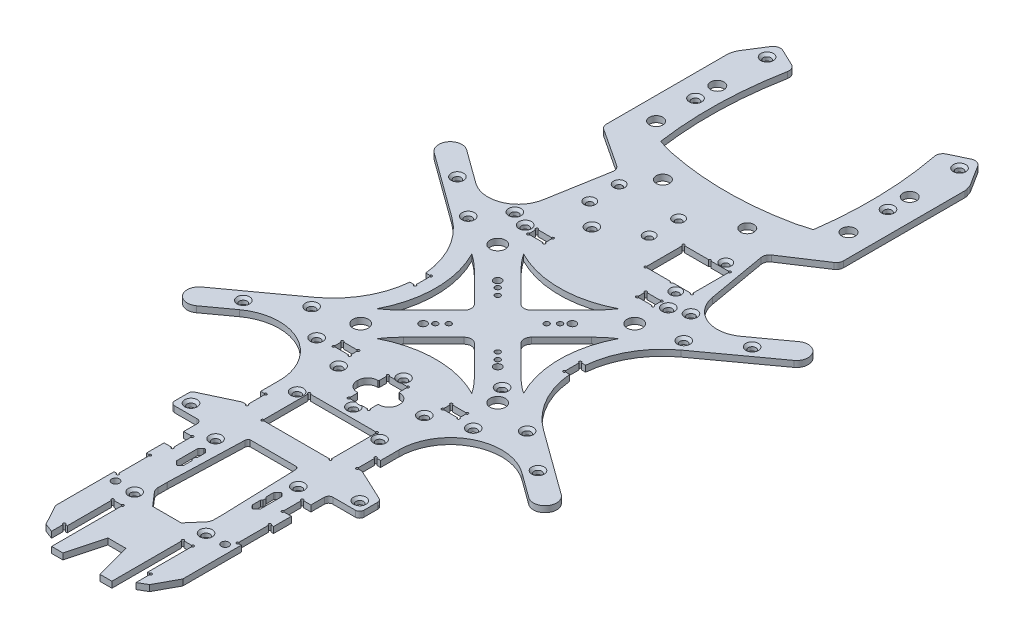
SolidWorks part; units mm, degrees
material "PPS"
ref_plane "前视基准面" through (0, 0, 0) normal (0, 0, 1) x (1, 0, 0)
ref_plane "上视基准面" through (0, 0, 0) normal (0, 1, 0) x (1, 0, 0)
ref_plane "右视基准面" through (0, 0, 0) normal (1, 0, 0) x (0, 0, -1)
sketch "草图1" plane through (0, 0, 0) normal (0, 1, 0) x (1, 0, 0)
  line L0 (-126.4995, 0) -> (116.8967, 0) construction
  line L1 (121.619, 121.619) -> (-121.619, -121.619) construction
  line L2 (0, 104.5414) -> (0, -99.6328) construction
  line L3 (-108.3893, 108.3893) -> (124.9236, -124.9236) construction
  line L4 (0, 0) -> (86.3378, -62.728) construction
  line L5 (21.4, 65.75) -> (28.6, 65.75)
  line L6 (20.9, 50.75) -> (20.9, 65.25)
  line L19 (21.4, 50.25) -> (28.6, 50.25)
  line L20 (30.0249, 79.2189) -> (48.4165, 91.3178)
  line L21 (0, 82.79) -> (0, 88.225) construction
  line L23 (-25.2781, 96.1111) -> (-31.2329, 97.7907)
  line L25 (24.5, -95.1) -> (26, -95.1) construction
  line L35 (73.5338, -47.5541) -> (46.853, -28.1694)
  line L38 (-14.1474, -105.2622) -> (-15.2326, -104.177)
  line L39 (-48.4165, 91.3178) -> (-48.4165, 143.0516)
  line L40 (-30.0249, 79.2189) -> (-48.4165, 91.3178)
  line L42 (26, -95.1) -> (26, -102.35)
  line L64 (20.9, 58) -> (32.4846, 58) construction
  line L65 (25, 65.75) -> (25, 50.25) construction
  line L66 (29.1, 65.25) -> (29.1, 50.75)
  line L69 (-39.335, 68.135) -> (3.7462, 68.135) construction
  line L72 (26, -102.35) -> (22.5, -102.35)
  line L80 (-15.9397, -104.177) -> (-16.9545, -105.1918)
  line L82 (4.1009, -56.25) -> (4.1009, -53.2975)
  line L83 (-3.6009, -56.75) -> (3.6009, -56.75)
  line L84 (3.6009, -40.75) -> (-3.5991, -40.75)
  line L85 (4.1009, -41.25) -> (4.1009, -44.2025)
  line L86 (-4.1009, -56.25) -> (-4.1009, -53.2961)
  line L87 (-4.1009, -44.2011) -> (-4.1009, -41.2481)
  line L88 (-4.5484, -52.9461) -> (-4.4509, -52.9461)
  line L89 (-8.5484, -48.9461) -> (-8.5484, -48.5511)
  line L90 (8.5484, -48.9475) -> (8.5484, -48.5525)
  line L91 (4.4509, -52.9475) -> (4.5484, -52.9475)
  line L92 (4.5484, -44.5525) -> (4.4509, -44.5525)
  line L93 (-4.5484, -44.5511) -> (-4.4509, -44.5511)
  line L97 (19, -62.5) -> (19, -100.5) construction
  line L98 (19, -100.5) -> (-19, -100.5) construction
  line L99 (-19, -62.5) -> (-19, -100.5) construction
  line L100 (22.5, -102.35) -> (22.5, -110.35)
  line L101 (16.4174, -141.0041) -> (16.4174, -159.5041)
  line L102 (16.4174, -141.0041) -> (12.3174, -141.0041)
  line L103 (12.3174, -141.0041) -> (12.3174, -170.0041)
  line L104 (17.705, -159.5041) -> (16.4174, -159.5041)
  line L105 (17.705, -165.5542) -> (17.705, -159.5041)
  line L106 (-3.8169, -155.5041) -> (-7.6919, -170.0041)
  line L107 (-7.6919, -170.0041) -> (-12.3174, -170.0041)
  line L108 (21.2406, -163.4622) -> (17.705, -165.5542)
  line L109 (-17.705, -164.6632) -> (-17.705, -159.5041)
  line L110 (-17.705, -159.5041) -> (-16.4174, -159.5041)
  line L111 (-12.3174, -141.0041) -> (-12.3174, -170.0041)
  line L112 (-16.4174, -141.0041) -> (-12.3174, -141.0041)
  line L113 (-16.4174, -141.0041) -> (-16.4174, -159.5041)
  line L114 (7.4592, -170.0041) -> (12.3174, -170.0041)
  line L115 (-3.8169, -155.5041) -> (3.6009, -155.5041)
  line L116 (3.6009, -155.5041) -> (7.4592, -170.0041)
  line L117 (-21.3412, -163.277) -> (-17.705, -164.6632)
  line L118 (-11.3955, -123.6362) -> (-10.3849, -92.9161)
  line L119 (-10.5767, -129.7197) -> (-5.85, -135.1929)
  line L120 (-5.85, -135.1929) -> (5.85, -135.1929)
  line L121 (-11.3974, -127.5138) -> (-11.3974, -123.7472)
  line L122 (22.5, -110.35) -> (26, -110.35)
  line L123 (26, -130.7962) -> (26, -154.7028)
  line L124 (26, -154.7028) -> (21.2406, -163.4622)
  line L125 (-26, -154.7028) -> (-21.3412, -163.277)
  line L126 (-26, -130.7962) -> (-26, -154.7028)
  line L127 (26, -110.35) -> (26, -117.6)
  line L128 (26, -117.6) -> (24.5, -117.6)
  line L129 (24.5, -117.6) -> (24.5, -130.7962)
  line L130 (24.5, -130.7962) -> (26, -130.7962)
  line L132 (-24.5, -130.7962) -> (-26, -130.7962)
  line L133 (-24.5, -117.6) -> (-24.5, -130.7962)
  line L134 (-26, -117.6) -> (-24.5, -117.6)
  line L135 (-26, -110.35) -> (-26, -117.6)
  line L136 (-22.5, -110.35) -> (-26, -110.35)
  line L137 (-22.5, -102.35) -> (-22.5, -110.35)
  line L138 (-26, -102.35) -> (-22.5, -102.35)
  line L139 (-26, -95.1) -> (-26, -102.35)
  line L140 (-24.5, -95.1) -> (-26, -95.1) construction
  line L142 (-73.5338, 47.5541) -> (-46.853, 28.1694)
  line L143 (-73.5338, -47.5541) -> (-46.853, -28.1694)
  line L149 (48.4165, 91.3178) -> (48.4165, 143.0516)
  line L150 (0, -114.8485) -> (0, -146.3095) construction
  line L151 (-9.5, -91.6929) -> (9.5, -91.6929)
  line L152 (10.5767, -129.7197) -> (5.85, -135.1929)
  line L153 (11.3974, -127.5138) -> (11.3974, -123.7472)
  line L154 (11.3955, -123.6362) -> (10.3849, -92.9161)
  line L155 (-19, -62.5) -> (19, -62.5) construction
  line L166 (-13.866, -63.21) -> (13.866, -63.21)
  line L171 (-13.866, -63.21) -> (-13.866, -82.21)
  line L174 (-13.866, -82.21) -> (13.866, -82.21)
  line L177 (13.866, -63.21) -> (13.866, -82.21)
  line L180 (73.5338, 47.5541) -> (46.853, 28.1694)
  line L181 (44.0442, 32) -> (60.2246, 43.7557) construction
  line L183 (25.2781, 96.1111) -> (31.2329, 97.7907)
  line L184 (47.6512, 145.4189) -> (48.4165, 143.0516)
  line L188 (-47.6512, 145.4189) -> (-40.8875, 156.1591)
  line L190 (47.6512, 145.4189) -> (40.8875, 156.1591)
  line L192 (31.6811, 151.7709) -> (40.8875, 156.1591)
  line L193 (-40.8875, 156.1591) -> (-31.6811, 151.7709)
  line L194 (-47.6512, 145.4189) -> (-48.4165, 143.0516)
  line L195 (67.9498, 55.2397) -> (54.1532, 45.2159)
  line L196 (30.0249, 79.2189) -> (34.5797, 53.1425)
  line L197 (-30.0249, 79.2189) -> (-34.5797, 53.1425)
  line L198 (-67.9498, 55.2397) -> (-54.1532, 45.2159)
  line L199 (57.77, -47.8437) -> (67.9498, -55.2397)
  line L200 (24.5, -64.7956) -> (24.5, -95.1) construction
  line L201 (-24.5, -64.7956) -> (-24.5, -95.1) construction
  line L202 (-57.77, -47.8437) -> (-67.9498, -55.2397)
  line L203 (26, -95.1) -> (38.6804, -95.1)
  line L204 (38.6804, -95.1) -> (38.6804, -86.6)
  line L205 (38.6804, -86.6) -> (24.5, -79.9478)
  line L207 (-38.6804, -86.6) -> (-24.5, -79.9478)
  line L208 (-38.6804, -95.1) -> (-38.6804, -86.6)
  line L209 (-26, -95.1) -> (-38.6804, -95.1)
  line L210 (-24.5, -64.7956) -> (-24.5, -79.9478) construction
  line L211 (-16.9545, -114.3989) -> (-15.8693, -115.4841)
  line L212 (-15.1622, -115.4841) -> (-14.1474, -114.4693)
  line L213 (-17.1009, -105.5454) -> (-17.1009, -114.0454)
  line L214 (-14.0009, -105.6158) -> (-14.0009, -114.1158) construction
  line L221 (-14.0009, -105.6158) -> (-14.0009, -108.6704)
  line L222 (-14.0009, -108.6704) -> (-14.5009, -109.1704)
  line L223 (-14.5009, -109.1704) -> (-14.5009, -110.4204)
  line L224 (-14.5009, -110.4204) -> (-14.0009, -110.9204)
  line L225 (-14.0009, -110.9204) -> (-14.0009, -114.1158)
  line L226 (-17.1009, -109.7954) -> (-13.2317, -109.7954) construction
  line L227 (14.5009, -110.4204) -> (14.0009, -110.9204)
  line L228 (14.5009, -109.1704) -> (14.5009, -110.4204)
  line L229 (14.0009, -108.6704) -> (14.5009, -109.1704)
  line L230 (14.0009, -105.6158) -> (14.0009, -108.6704)
  line L231 (14.1474, -105.2622) -> (15.2326, -104.177)
  line L232 (15.9397, -104.177) -> (16.9545, -105.1918)
  line L233 (17.1009, -105.5454) -> (17.1009, -114.0454)
  line L234 (16.9545, -114.3989) -> (15.8693, -115.4841)
  line L235 (15.1622, -115.4841) -> (14.1474, -114.4693)
  line L236 (14.0009, -110.9204) -> (14.0009, -114.1158)
  line L237 (-24.5, -72.3717) -> (-22.5, -72.3717)
  line L238 (-22.5, -72.3717) -> (-22.5, -79.9478)
  line L239 (-22.5, -79.9478) -> (-24.5, -79.9478)
  line L240 (-24.5, -64.7956) -> (-24.5, -72.3717)
  line L241 (22.5, -79.9478) -> (24.5, -79.9478)
  line L242 (24.5, -64.7956) -> (24.5, -72.3717)
  line L243 (24.5, -72.3717) -> (22.5, -72.3717)
  line L244 (22.5, -72.3717) -> (22.5, -79.9478)
  circle A0 centre (10, 10) radius 1.075
  circle A1 centre (12.75, 12.75) radius 1.075
  circle A2 centre (15.25, 15.25) radius 1.55
  circle A3 centre (-15.25, 15.25) radius 1.55
  circle A4 centre (-12.75, 12.75) radius 1.075
  circle A5 centre (-10, 10) radius 1.075
  circle A6 centre (-10, -10) radius 1.075
  circle A7 centre (-12.75, -12.75) radius 1.075
  circle A8 centre (-15.25, -15.25) radius 1.55
  circle A9 centre (15.25, -15.25) radius 1.55
  circle A10 centre (12.75, -12.75) radius 1.075
  circle A11 centre (10, -10) radius 1.075
  circle A14 centre (28, -28) radius 3.15
  circle A15 centre (-28, -28) radius 3.15
  circle A16 centre (25, 68.2) radius 1.3
  arc A17 (20.9, 65.25) -> (21.4, 65.75) centre (20.9, 65.75) cw
  arc A18 (20.9, 50.75) -> (21.4, 50.25) centre (20.9, 50.25) ccw
  circle A31 centre (25, 47.8) radius 1.3
  circle A34 centre (17.238, 84.7633) radius 2.75
  circle A35 centre (-17.238, 84.7633) radius 2.75
  circle A36 centre (-39.335, 104.0823) radius 2.75
  circle A37 centre (-39.335, 129.0823) radius 2.75
  circle A38 centre (-28, 28) radius 3.15
  circle A39 centre (28, 28) radius 3.15
  circle A43 centre (44.0442, -32) radius 1.55
  circle A44 centre (60.2246, -43.7557) radius 1.55
  circle A47 centre (-60.2246, -43.7557) radius 1.55
  arc A63 (29.1, 65.25) -> (28.6, 65.75) centre (29.1, 65.75) ccw
  arc A64 (29.1, 50.75) -> (28.6, 50.25) centre (29.1, 50.25) cw
  circle A65 centre (-24.5, 74.15) radius 1.3
  circle A68 centre (-24.5, 62.12) radius 1.3
  circle A71 centre (-44.0442, -32) radius 1.55
  circle A72 centre (60.2246, 43.7557) radius 1.55
  circle A73 centre (44.0442, 32) radius 1.55
  circle A74 centre (-44.0442, 32) radius 1.55
  circle A75 centre (-60.2246, 43.7557) radius 1.55
  arc A77 (67.9498, -55.2397) -> (73.5338, -47.5541) centre (70.7418, -51.3969) ccw
  arc A82 (-14.0009, -105.6158) -> (-14.1474, -105.2622) centre (-14.5009, -105.6158) ccw
  arc A83 (-15.2326, -104.177) -> (-15.9397, -104.177) centre (-15.5861, -104.5306) ccw
  arc A84 (-17.1009, -105.5454) -> (-16.9545, -105.1918) centre (-16.6009, -105.5454) cw
  arc A85 (-4.1009, -56.25) -> (-3.6009, -56.75) centre (-4.1009, -56.75) ccw
  arc A86 (4.1009, -56.25) -> (3.6009, -56.75) centre (4.1009, -56.75) cw
  arc A87 (4.1009, -41.25) -> (3.6009, -40.75) centre (4.1009, -40.75) ccw
  arc A88 (-4.1009, -41.2481) -> (-3.5991, -40.75) centre (-4.0991, -40.7481) cw
  arc A89 (8.5484, -48.5525) -> (4.5484, -44.5525) centre (4.5484, -48.5525) ccw
  arc A90 (-4.5484, -44.5511) -> (-8.5484, -48.5511) centre (-4.5484, -48.5511) ccw
  arc A91 (-4.5484, -52.9461) -> (-8.5484, -48.9461) centre (-4.5484, -48.9461) cw
  arc A92 (8.5484, -48.9475) -> (4.5484, -52.9475) centre (4.5484, -48.9475) cw
  arc A93 (4.1009, -44.2025) -> (4.4509, -44.5525) centre (4.4509, -44.2025) ccw
  arc A94 (4.1009, -53.2975) -> (4.4509, -52.9475) centre (4.4509, -53.2975) cw
  arc A95 (-4.1009, -44.2011) -> (-4.4509, -44.5511) centre (-4.4509, -44.2011) cw
  arc A96 (-4.1009, -53.2961) -> (-4.4509, -52.9461) centre (-4.4509, -53.2961) ccw
  circle A103 centre (-22.3899, -133.8062) radius 1.55
  circle A104 centre (22.3899, -133.8062) radius 1.55
  circle A105 centre (-16.9, -98.4) radius 1.55
  circle A106 centre (16.9, -98.4) radius 1.55
  arc A107 (-9.5, -91.6929) -> (-10.3849, -92.9161) centre (-9.0356, -92.9605) ccw
  arc A108 (-11.3974, -123.7472) -> (-11.3955, -123.6362) centre (-8.0224, -123.7472) cw
  arc A109 (-10.5767, -129.7197) -> (-11.3974, -127.5138) centre (-8.0224, -127.5138) cw
  circle A110 centre (-14.6009, -133.8062) radius 1.55
  circle A111 centre (14.6009, -133.8062) radius 1.55
  arc A112 (10.5767, -129.7197) -> (11.3974, -127.5138) centre (8.0224, -127.5138) ccw
  arc A113 (11.3974, -123.7472) -> (11.3955, -123.6362) centre (8.0224, -123.7472) ccw
  arc A114 (9.5, -91.6929) -> (10.3849, -92.9161) centre (9.0356, -92.9605) cw
  circle A143 centre (-16.866, -65.108) radius 1.55
  circle A144 centre (16.866, -65.108) radius 1.55
  circle A145 centre (0, -38.5) radius 1.55
  circle A146 centre (0, -59) radius 1.55
  arc A147 (67.9498, 55.2397) -> (73.5338, 47.5541) centre (70.7418, 51.3969) cw
  arc A148 (46.853, 28.1694) -> (46.853, -28.1694) centre (67.3193, 0) ccw
  circle A149 centre (44.0442, -32) radius 6 construction
  arc A151 (-67.9498, 55.2397) -> (-73.5338, 47.5541) centre (-70.7418, 51.3969) ccw
  arc A153 (-46.853, 28.1694) -> (-46.853, -28.1694) centre (-67.3193, 0) cw
  arc A154 (-67.9498, -55.2397) -> (-73.5338, -47.5541) centre (-70.7418, -51.3969) cw
  circle A158 centre (39.335, 129.0823) radius 2.75
  circle A159 centre (39.335, 104.0823) radius 2.75
  arc A160 (-25.2781, 96.1111) -> (25.2781, 96.1111) centre (0, 215.2587) ccw
  circle A161 centre (-36, 43) radius 1.55
  circle A164 centre (36, 43) radius 1.55
  circle A165 centre (-32, -42) radius 1.55
  circle A166 centre (32, -42) radius 1.55
  circle A171 centre (-39.335, 149.4323) radius 1.55
  arc A176 (30.0249, 148.5011) -> (31.6811, 151.7709) centre (32.9719, 149.0628) cw
  arc A178 (30.0249, 148.5011) -> (31.2329, 97.7907) centre (-122.0773, 119.5082) cw
  arc A180 (-30.0249, 148.5011) -> (-31.2329, 97.7907) centre (122.0773, 119.5082) ccw
  arc A181 (-31.6811, 151.7709) -> (-30.0249, 148.5011) centre (-32.9719, 149.0628) cw
  arc A182 (54.1532, 45.2159) -> (34.5797, 53.1425) centre (46.8385, 55.2837) cw
  arc A183 (-54.1532, 45.2159) -> (-34.5797, 53.1425) centre (-46.8385, 55.2837) ccw
  circle A185 centre (39.335, 149.4323) radius 1.55
  arc A186 (57.77, -47.8437) -> (24.5, -64.7956) centre (45.4537, -64.7956) ccw
  arc A187 (-57.77, -47.8437) -> (-24.5, -64.7956) centre (-45.4537, -64.7956) cw
  circle A188 centre (34.5, -90.85) radius 1.55
  circle A189 centre (-34.5, -90.85) radius 1.55
  circle A190 centre (39.335, 120.1823) radius 1.55
  circle A191 centre (-39.335, 120.1823) radius 1.55
  arc A192 (-17.1009, -114.0454) -> (-16.9545, -114.3989) centre (-16.6009, -114.0454) ccw
  arc A193 (-15.8693, -115.4841) -> (-15.1622, -115.4841) centre (-15.5157, -115.1306) ccw
  arc A194 (-14.0009, -114.1158) -> (-14.1474, -114.4693) centre (-14.5009, -114.1158) cw
  arc A195 (14.0009, -105.6158) -> (14.1474, -105.2622) centre (14.5009, -105.6158) cw
  arc A196 (15.2326, -104.177) -> (15.9397, -104.177) centre (15.5861, -104.5306) cw
  arc A197 (17.1009, -105.5454) -> (16.9545, -105.1918) centre (16.6009, -105.5454) ccw
  arc A198 (17.1009, -114.0454) -> (16.9545, -114.3989) centre (16.6009, -114.0454) cw
  arc A199 (15.8693, -115.4841) -> (15.1622, -115.4841) centre (15.5157, -115.1306) cw
  arc A200 (14.0009, -114.1158) -> (14.1474, -114.4693) centre (14.5009, -114.1158) ccw
  circle A201 centre (-0.2, 62.12) radius 1.3
  circle A202 centre (-0.2, 74.15) radius 1.3
  point P104 (-32.5, 0)
  point P105 (32.5, 0)
  point P214 (38.6804, -90.85)
  point P354 (0, -135.1929)
  point P361 (7.3036, -118.1341)
  point P364 (0, -91.6929)
  dimension "D2" = 2.15
  dimension "D5" = 3.1
  dimension "D7" = 3.1
  dimension "D8" = 36
  dimension "D10" = 0.5
  dimension "D11" = 3.1
  dimension "D20" = 2.6
  dimension "D22" = 3.1
  dimension "D32" = 7.25
  dimension "D12" = 24.3
  dimension "D15" = 19
  dimension "D13" = 3
  dimension "D9" = 3.1
  dimension "D25" = 4.75
  dimension "D26" = 13
  dimension "D31" = 12
  dimension "D41" = 96.833
  dimension "D49" = 32
  dimension "D54" = 45.35
  dimension "D59" = 8.5
  dimension "D61" = 6.3
  dimension "D70" = 2.6
  dimension "D3" = 10
  dimension "D4" = 2.75
  dimension "D6" = 2.5
  dimension "D14" = 58
  dimension "D16" = 2.608
  dimension "D17" = 15.5
  dimension "D18" = 2.45
  dimension "D19" = 8.2
  dimension "D21" = 12.03
  dimension "D23" = 2.25
  dimension "D24" = 2.25
  dimension "D27" = 20
  dimension "D28" = 25
  dimension "D29" = 25
  dimension "D30" = 32
  dimension "D33" = 1.5
  dimension "D34" = 2.1
  dimension "D35" = 10.5
  dimension "D36" = 14.5
  dimension "D37" = 4
  dimension "D38" = 4.1
  dimension "D39" = 8
  dimension "D40" = 65
  dimension "D42" = 9.5
  dimension "D43" = 43
  dimension "D44" = 43.5
  dimension "D45" = 40.75
  dimension "D46" = 7.2
  dimension "D47" = 16
  dimension "D48" = 62.5
  dimension "D50" = 38
  dimension "D51" = 7.2
  dimension "D52" = 36
  dimension "D53" = 42
  dimension "D55" = 90.85
  dimension "D56" = 5.5
  dimension "D57" = 38
  dimension "D58" = 34.5
  dimension "D60" = 56
  dimension "D62" = 5.85
  dimension "D63" = 29.25
  dimension "D64" = 8.5
  dimension "D65" = 1.25
  dimension "D66" = 0.5
  dimension "D67" = 2
  dimension "D68" = 24.5
  dimension "D69" = 82.21
extrude "凸台-拉伸1" add sketch "草图1" along normal blind 2.5
sketch "草图6" plane through (0, 2.5, 0) normal (0, 1, 0) x (1, 0, 0)
  line L1 (-23.978, 14.4296) -> (-9.5485, 0)
  line L2 (-126.4995, 0) -> (116.8967, 0) construction
  line L3 (-58.8867, 0) -> (57.6096, 0) construction
  line L4 (-23.978, -14.4296) -> (-9.5485, 0)
  line L5 (0, 29.8455) -> (0, -115.5328) construction
  line L6 (0, 104.5414) -> (0, -99.6328) construction
  line L14 (14.4296, 23.978) -> (0, 9.5485)
  line L15 (-14.4296, 23.978) -> (0, 9.5485)
  line L27 (23.978, -14.4296) -> (9.5485, 0)
  line L28 (23.978, 14.4296) -> (9.5485, 0)
  line L29 (-14.4296, -23.978) -> (0, -9.5485)
  line L30 (14.4296, -23.978) -> (0, -9.5485)
  arc A3 (-23.978, 14.4296) -> (-29.9602, 19.3706) centre (-52.8883, -14.4807) ccw
  arc A5 (-23.978, -14.4296) -> (-29.9602, -19.3706) centre (-52.8883, 14.4807) cw
  arc A6 (-29.9602, -19.3706) -> (-29.9602, 19.3706) centre (-67.3193, 0) ccw
  arc A18 (-14.4296, 23.978) -> (-19.3706, 29.9602) centre (14.4807, 52.8883) cw
  arc A19 (-19.3706, 29.9602) -> (19.3706, 29.9602) centre (0, 67.3193) ccw
  arc A20 (14.4296, 23.978) -> (19.3706, 29.9602) centre (-14.4807, 52.8883) ccw
  arc A30 (23.978, 14.4296) -> (29.9602, 19.3706) centre (52.8883, -14.4807) cw
  arc A31 (29.9602, 19.3706) -> (29.9602, -19.3706) centre (67.3193, 0) ccw
  arc A32 (23.978, -14.4296) -> (29.9602, -19.3706) centre (52.8883, 14.4807) ccw
  arc A33 (14.4296, -23.978) -> (19.3706, -29.9602) centre (-14.4807, -52.8883) cw
  arc A34 (19.3706, -29.9602) -> (-19.3706, -29.9602) centre (0, -67.3193) ccw
  arc A35 (-14.4296, -23.978) -> (-19.3706, -29.9602) centre (14.4807, -52.8883) ccw
  dimension "D1" = 45
  dimension "D2" = 4
extrude "减重" cut sketch "草图6" against normal up to next
fillet "圆角1" radius 3 14 edges at (-25.2781, 1.25, -96.1111) (25.2781, 1.25, -96.1111) (48.4165, 1.25, -91.3178) (-48.4165, 1.25, -91.3178) (-9.5485, 1.25, 0) (9.5485, 1.25, 0) (0, 1.25, -9.5485) (0, 1.25, 9.5485) (48.4165, 1.25, -143.0516) (40.8875, 1.25, -156.1591) (-48.4165, 1.25, -143.0516) (-40.8875, 1.25, -156.1591) (-30.0249, 1.25, -79.2189) (30.0249, 1.25, -79.2189)
sketch "草图7" plane through (0, 2.5, 0) normal (0, 1, 0) x (1, 0, 0)
  line L0 (-81.2345, 0) -> (102.1666, 0) construction
  line L1 (0, 63.5408) -> (0, -83.9036) construction
  line L2 (34, -3.25) -> (30.5, -3.25)
  line L3 (-34, 3.25) -> (-30.5, 3.25)
  line L4 (-34, 3.25) -> (-34, -3.25)
  line L5 (-34, -3.25) -> (-30.5, -3.25)
  line L6 (-30.5, 3.25) -> (-30.5, -3.25)
  line L7 (30.5, 3.25) -> (30.5, -3.25)
  line L8 (34, 3.25) -> (30.5, 3.25)
  line L9 (34, 3.25) -> (34, -3.25)
  line L10 (19, -38) -> (25.5, -38)
  line L11 (-25.5, 41.5) -> (-19, 41.5)
  line L12 (-25.5, 41.5) -> (-25.5, 38)
  line L13 (-25.5, 38) -> (-19, 38)
  line L14 (-19, 41.5) -> (-19, 38)
  line L15 (19, -38) -> (19, -41.5)
  line L16 (19, -41.5) -> (25.5, -41.5)
  line L17 (25.5, -38) -> (25.5, -41.5)
  line L18 (-19, -38) -> (-19, -41.5)
  line L19 (-19, -41.5) -> (-25.5, -41.5)
  line L20 (-25.5, -38) -> (-25.5, -41.5)
  line L21 (-19, -38) -> (-25.5, -38)
  line L22 (25.5, 38) -> (19, 38)
  line L23 (19, 41.5) -> (19, 38)
  line L24 (25.5, 41.5) -> (19, 41.5)
  line L25 (25.5, 41.5) -> (25.5, 38)
  point P26 (19, -39.75)
  dimension "D1" = 3.5
  dimension "D2" = 6.5
  dimension "D3" = 30.5
  dimension "D4" = 38
  dimension "D5" = 19
  dimension "D6" = 38
extrude "保护壳固定点" cut sketch "草图7" against normal up to next
sketch "草图8" plane through (0, 0, 0) normal (0, 1, 0) x (1, 0, 0)
  line L5 (0, 0) -> (0, 133.3353) construction
  line L6 (0, 0) -> (133.1914, 0) construction
  line L7 (10.15, 65.7804) -> (20.9, 65.7804)
  line L8 (20.9, 65.25) -> (20.9, 50.75) construction
  line L9 (20.9, 65.7804) -> (20.9, 50.2804)
  line L10 (20.9, 50.2804) -> (10.15, 50.2804)
  line L11 (10.15, 50.2804) -> (10.15, 65.7804)
  line L12 (19.65, 65.7804) -> (19.65, 50.2804) construction
  circle A0 centre (23.5, -21.7128) radius 1.55
  circle A1 centre (0, -38.5) radius 1.55 construction
  circle A2 centre (-29.25, 40.5) radius 1.55
  circle A4 centre (-17.5, -47.5) radius 1.55
  circle A6 centre (29.25, 40.5) radius 1.55
  circle A7 centre (17.5, -47.5) radius 1.55
  circle A8 centre (29.25, 40.5) radius 1.55
  dimension "D3" = 3.1
  dimension "D9" = 40.5
  dimension "D12" = 3.1
  dimension "D1" = 16.7872
  dimension "D2" = 23.5
  dimension "D4" = 1.25
  dimension "D6" = 9.5
  dimension "D7" = 15.5
  dimension "D8" = 29.25
  dimension "D10" = 47.5
  dimension "D11" = 17.5
extrude "计算机板接口和分电PCB接口" cut sketch "草图8" along normal through all contours L11 L10 L9 L7 | A2 | A4 | A7 | A6 | A0 | A0 region at (15.525, 0, -58.0304) region at (23.5, 0, 21.7128) region at (-29.25, 0, -40.5) region at (-17.5, 0, 47.5) region at (29.25, 0, -40.5) region at (17.5, 0, 47.5)
fillet "圆角2" radius 1.75 8 edges at (-26, 1.25, 95.1) (-38.6804, 1.25, 95.1) (-38.6804, 1.25, 86.6) (38.6804, 1.25, 86.6) (38.6804, 1.25, 95.1) (26, 1.25, 95.1) (24.5, 1.25, 79.9478) (-24.5, 1.25, 79.9478)
chamfer "沉头螺丝位" distance 1 angle 45 37 edges at (14.6009, 2.5, 135.3562) (-14.6009, 2.5, 132.2562) (0, 2.5, 40.05) (0, 2.5, 60.55) (25, 2.5, -49.1) (25, 2.5, -69.5) (-24.5, 2.5, -63.42) (-24.5, 2.5, -72.85) (60.2246, 2.5, -45.3057) (44.0442, 2.5, -33.55) (36, 2.5, -44.55) (-60.2246, 2.5, -42.2057) (-36, 2.5, -41.45) (-44.0442, 2.5, -30.45) (-32, 2.5, 43.55) (-44.0442, 2.5, 30.45) (-60.2246, 2.5, 42.2057) (60.2246, 2.5, 45.3057) (44.0442, 2.5, 33.55) (32, 2.5, 40.45) (16.866, 2.5, 63.558) (-16.866, 2.5, 66.658) (-16.9, 2.5, 99.95) (16.9, 2.5, 96.85) (34.5, 2.5, 92.4) (-34.5, 2.5, 89.3) (39.335, 2.5, -147.8823) (-39.335, 2.5, -147.8823) (23.5, 2.5, 23.2628) (29.25, 2.5, -38.95) (-29.25, 2.5, -38.95) (-17.5, 2.5, 49.05) (17.5, 2.5, 49.05) (39.335, 2.5, -118.6323) (-39.335, 2.5, -121.7323) (-0.2, 2.5, -75.45) (-0.2, 2.5, -60.82)
sketch "这个是因为刀切不了直角" plane through (0, 2.5, 0) normal (0, 1, 0) x (1, 0, 0)
  line L1 (-17.705, -164.6632) -> (-17.705, -159.5041) construction
  line L2 (0, 0) -> (0, -194.9857) construction
  circle A0 centre (10.15, 65.7804) radius 0.5
  circle A1 centre (10.15, 50.2804) radius 0.5
  circle A2 centre (-25.5, 41.5) radius 0.5
  circle A3 centre (-19, 41.5) radius 0.5
  circle A4 centre (-25.5, 38) radius 0.5
  circle A5 centre (-19, 38) radius 0.5
  circle A14 centre (-25.5, -38) radius 0.5
  circle A15 centre (-19, -38) radius 0.5
  circle A16 centre (-25.5, -41.5) radius 0.5
  circle A17 centre (-19, -41.5) radius 0.5
  circle A28 centre (-13.866, -82.21) radius 0.5
  circle A30 centre (-13.866, -63.21) radius 0.5
  circle A31 centre (-22.5, -72.3717) radius 0.5
  circle A33 centre (-22.5, -79.9478) radius 0.5
  circle A35 centre (-22.5, -102.35) radius 0.5
  circle A37 centre (-22.5, -110.35) radius 0.5
  circle A39 centre (-24.5, -117.6) radius 0.5
  circle A40 centre (-16.4174, -141.0041) radius 0.5
  circle A41 centre (-24.5, -130.7962) radius 0.5
  circle A42 centre (-12.3174, -141.0041) radius 0.5
  circle A43 centre (-17.705, -159.5041) radius 0.5
  circle A47 centre (17.705, -159.5041) radius 0.5
  circle A48 centre (12.3174, -141.0041) radius 0.5
  circle A49 centre (24.5, -130.7962) radius 0.5
  circle A50 centre (16.4174, -141.0041) radius 0.5
  circle A51 centre (24.5, -117.6) radius 0.5
  circle A52 centre (22.5, -110.35) radius 0.5
  circle A53 centre (22.5, -102.35) radius 0.5
  circle A54 centre (22.5, -79.9478) radius 0.5
  circle A55 centre (22.5, -72.3717) radius 0.5
  circle A57 centre (13.866, -82.21) radius 0.5
  circle A58 centre (19, -41.5) radius 0.5
  circle A59 centre (25.5, -41.5) radius 0.5
  circle A60 centre (19, -38) radius 0.5
  circle A61 centre (25.5, -38) radius 0.5
  circle A62 centre (19, 38) radius 0.5
  circle A63 centre (25.5, 38) radius 0.5
  circle A64 centre (19, 41.5) radius 0.5
  circle A65 centre (25.5, 41.5) radius 0.5
  circle A66 centre (13.866, -63.21) radius 0.5
  circle A67 centre (-30.5, 3.25) radius 0.5
  circle A69 centre (-30.5, -3.25) radius 0.5
  circle A70 centre (30.5, -3.25) radius 0.5
  circle A71 centre (30.5, 3.25) radius 0.5
  dimension "D1" = 1
extrude "直角约束" cut sketch "这个是因为刀切不了直角" against normal through all
sketch "草图9" plane through (0, 2.5, 0) normal (0, 1, 0) x (1, 0, 0)
  line L0 (26.7, 40.5) -> (-26.7, 40.5) construction
  circle A0 centre (29.25, 40.5) radius 2.55 construction
  circle A1 centre (-29.25, 40.5) radius 2.55 construction
  circle A10 centre (-15, 53.5) radius 1.55
extrude "切除-拉伸2" cut sketch "草图9" against normal blind 10
chamfer "倒角3" distance 1 angle 45 1 edges at (-15, 2.5, -51.95)
